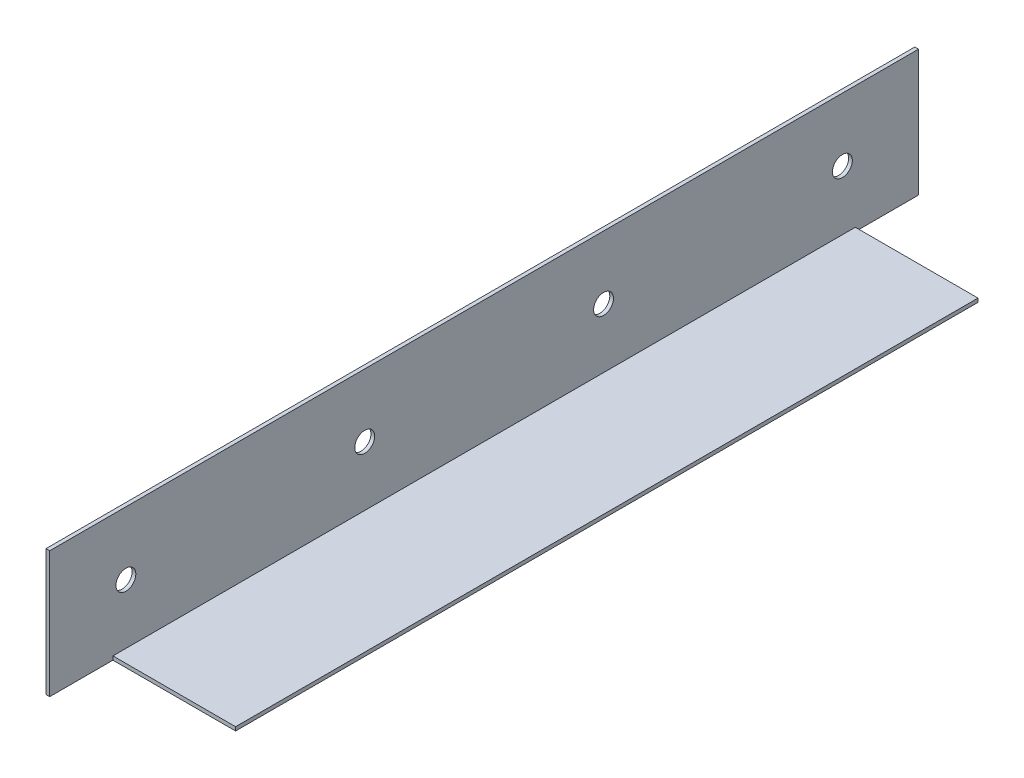
SolidWorks part; units mm, degrees
material "AISI 1015 Acero estirado en frío (SS)"
ref_plane "Alzado" through (0, 0, 0) normal (0, 0, 1) x (1, 0, 0)
ref_plane "Planta" through (0, 0, 0) normal (0, 1, 0) x (1, 0, 0)
ref_plane "Vista lateral" through (0, 0, 0) normal (1, 0, 0) x (0, 0, -1)
sketch "Croquis1" plane through (0, 0, 0) normal (0, 0, 1) x (1, 0, 0)
  line L0 (0, 0) -> (0, 50.8)
  line L1 (0, 0) -> (50.8, 0)
  line L2 (1.5, 1.5) -> (50.8, 1.5)
  line L3 (1.5, 1.5) -> (1.5, 50.8)
  line L4 (1.5, 50.8) -> (0, 50.8)
  line L5 (50.8, 1.5) -> (50.8, 0)
  dimension "D1" = 50.8
  dimension "D2" = 1.5
extrude "Saliente-Extruir1" add sketch "Croquis1" along normal blind 349.2
sketch "Croquis2" plane through (0, 0, 0) normal (-1, 0, 0) x (0, 0, 1)
  line L0 (349.2, 25.4) -> (-34.0342, 25.4) construction
  line L1 (349.2, 50.8) -> (349.2, 0) construction
  line L2 (174.6, 0) -> (174.6, 64.0617) construction
  line L3 (349.2, 0) -> (0, 0) construction
  circle A0 centre (126.6, 25.4) radius 4
  circle A1 centre (222.6, 25.4) radius 4
  circle A2 centre (30.6, 25.4) radius 4
  circle A3 centre (318.6, 25.4) radius 4
  dimension "D1" = 8
  dimension "D2" = 48
  dimension "D3" = 48
  dimension "D4" = 96
  dimension "D5" = 96
extrude "Cortar-Extruir1" cut sketch "Croquis2" against normal blind 2
sketch "Croquis4" plane through (0, 1.5, 0) normal (0, 1, 0) x (1, 0, 0)
  line L0 (1.5, 0) -> (1.5, -25.4)
  line L1 (1.5, -349.2) -> (1.5, 0) construction
  line L2 (1.5, -25.4) -> (50.8, -25.4)
  line L3 (50.8, -349.2) -> (50.8, 0) construction
  line L4 (50.8, -25.4) -> (50.8, 0)
  line L5 (50.8, 0) -> (1.5, 0)
  line L6 (50.8, -174.6) -> (-84.9602, -174.6) construction
  line L7 (1.5, -349.2) -> (1.5, -323.8)
  line L8 (50.8, -349.2) -> (1.5, -349.2)
  line L9 (50.8, -323.8) -> (50.8, -349.2)
  line L10 (1.5, -323.8) -> (50.8, -323.8)
  dimension "D1" = 25.4
  dimension "D2" = 49.3
extrude "Cortar-Extruir2" cut sketch "Croquis4" against normal blind 2
